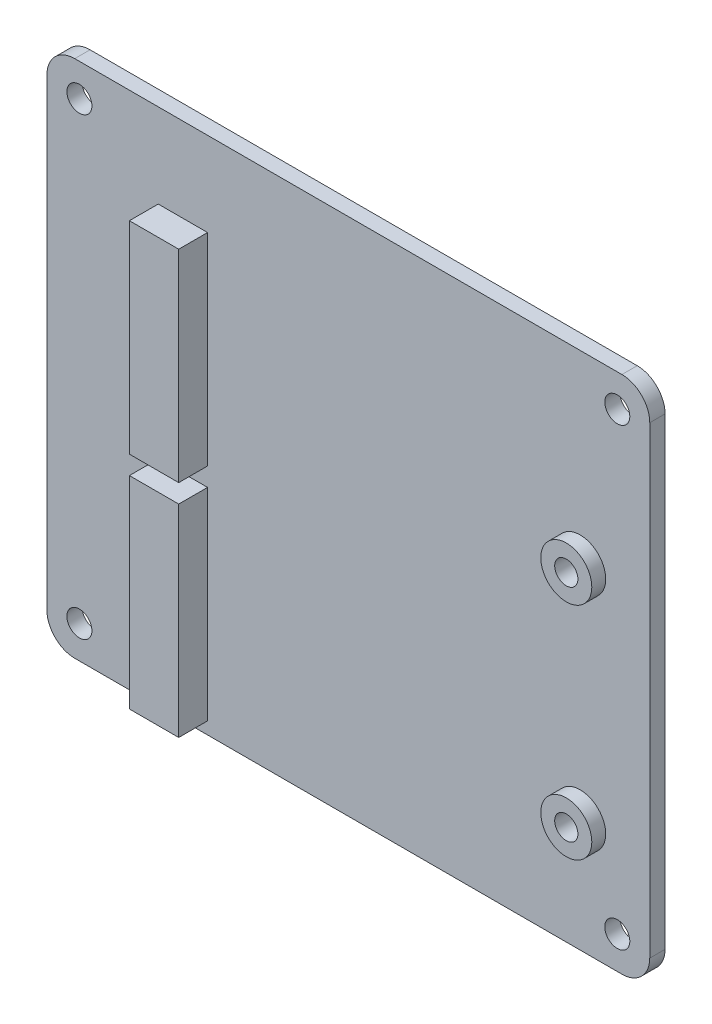
SolidWorks part; units mm, degrees
ref_plane "前视基准面" through (0, 0, 0) normal (0, 0, 1) x (1, 0, 0)
ref_plane "上视基准面" through (0, 0, 0) normal (0, 1, 0) x (1, 0, 0)
ref_plane "右视基准面" through (0, 0, 0) normal (1, 0, 0) x (0, 0, -1)
other "Configuration Table"
sketch "草图1" plane through (23.5903, 87.7411, -201.3211) normal (0, 0, 1) x (1, 0, 0)
  line L1 (-93.3542, 91.4857) -> (-34.3542, 91.4857)
  line L2 (-96.3542, 88.4857) -> (-96.3542, 38.4857)
  line L3 (-93.3542, 35.4857) -> (-34.3542, 35.4857)
  line L4 (-31.3542, 88.4857) -> (-31.3542, 38.4857)
  arc A0 (-34.3542, 91.4857) -> (-31.3542, 88.4857) centre (-34.3542, 88.4857) cw
  arc A1 (-34.3542, 35.4857) -> (-31.3542, 38.4857) centre (-34.3542, 38.4857) ccw
  arc A2 (-96.3542, 38.4857) -> (-93.3542, 35.4857) centre (-93.3542, 38.4857) ccw
  arc A3 (-93.3542, 91.4857) -> (-96.3542, 88.4857) centre (-93.3542, 88.4857) ccw
  point P6 (-31.3542, 91.4857)
  point P11 (-96.3542, 35.4857)
  point P14 (-96.3542, 91.4857)
  dimension "D3" = 3
  dimension "D1" = 65
  dimension "D2" = 56
extrude "凸台-拉伸1" add sketch "草图1" along normal blind 1.65
sketch "草图2" plane through (0, 0, -199.6711) normal (0, 0, 1) x (1, 0, 0)
  line L1 (-10.7639, 179.2268) -> (-69.7639, 179.2268) construction
  line L2 (-69.7639, 123.2268) -> (-10.7639, 123.2268) construction
  line L3 (-7.7639, 126.2268) -> (-7.7639, 176.2268) construction
  line L4 (-72.7639, 176.2268) -> (-72.7639, 126.2268) construction
  circle A0 centre (-69.2639, 175.7268) radius 1.35
  circle A1 centre (-11.2639, 175.7268) radius 1.35
  circle A2 centre (-69.2639, 126.7268) radius 1.35
  circle A3 centre (-11.2639, 126.7268) radius 1.35
  point P12 (0, 0)
  point P13 (0, 0)
  point P14 (0, 0)
  point P15 (0, 0)
  point P24 (0, 0)
  point P25 (0, 0)
  point P26 (0, 0)
  point P27 (0, 0)
  dimension "D1" = 2.7
  dimension "D2" = 3.5
  dimension "D3" = 3.5
  dimension "D4" = 3.5
  dimension "D5" = 3.5
extrude "切除-拉伸1" cut sketch "草图2" against normal blind 1.65
sketch "草图3" plane through (0, 0, -199.6711) normal (0, 0, 1) x (1, 0, 0)
  line L0 (-69.7639, 123.2268) -> (-10.7639, 123.2268) construction
  line L1 (-60.7639, 170.1468) -> (-55.4439, 170.1468)
  line L2 (-60.7639, 170.1468) -> (-60.7639, 148.3468)
  line L3 (-60.7639, 148.3468) -> (-55.4439, 148.3468)
  line L4 (-55.4439, 170.1468) -> (-55.4439, 148.3468)
  line L5 (-60.7639, 146.3468) -> (-55.4439, 146.3468)
  line L6 (-60.7639, 146.3468) -> (-60.7639, 124.5468)
  line L7 (-60.7639, 124.5468) -> (-55.4439, 124.5468)
  line L8 (-55.4439, 146.3468) -> (-55.4439, 124.5468)
  line L9 (-72.7639, 176.2268) -> (-72.7639, 126.2268) construction
  point P8 (-66.5905, 146.3468)
  dimension "D1" = 21.8
  dimension "D2" = 5.32
  dimension "D3" = 1.32
  dimension "D4" = 2
  dimension "D5" = 12
extrude "凸台-拉伸2" add sketch "草图3" along normal blind 3.11
sketch "草图4" plane through (0, 0, -199.6711) normal (0, 0, 1) x (1, 0, 0)
  line L0 (-55.4439, 148.3468) -> (-55.4439, 170.1468) construction
  line L1 (-55.4439, 124.5468) -> (-55.4439, 146.3468) construction
  line L2 (-7.7639, 126.2268) -> (-7.7639, 176.2268) construction
  circle A0 centre (-15.2639, 135.4468) radius 2.75
  circle A1 centre (-15.2639, 159.2468) radius 2.75
  point P6 (-55.4439, 159.2468)
  point P7 (0, 0)
  point P10 (-55.4439, 135.4468)
  point P11 (-55.4439, 135.4468)
  point P12 (-23.1381, 135.4468)
  dimension "D1" = 5.5
  dimension "D2" = 7.5
extrude "凸台-拉伸3" add sketch "草图4" along normal blind 1.5
sketch "草图5" plane through (0, 0, -198.1711) normal (0, 0, 1) x (1, 0, 0)
  circle A0 centre (-15.2639, 159.2468) radius 1.25
  circle A1 centre (-15.2639, 135.4468) radius 1.25
  dimension "D1" = 2.5
extrude "切除-拉伸2" cut sketch "草图5" against normal up to next
